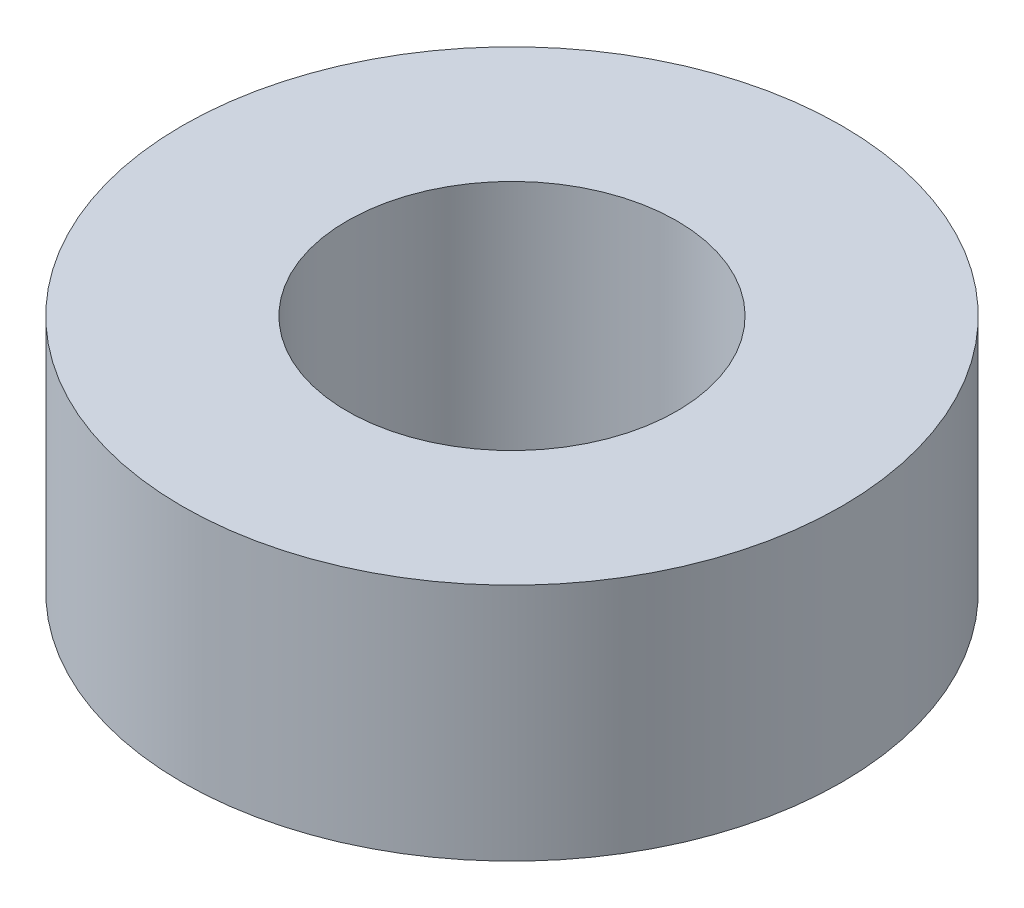
SolidWorks part; units mm, degrees
ref_plane "Front Plane" through (0, 0, 0) normal (0, 0, 1) x (1, 0, 0)
ref_plane "Top Plane" through (0, 0, 0) normal (0, 1, 0) x (1, 0, 0)
ref_plane "Right Plane" through (0, 0, 0) normal (1, 0, 0) x (0, 0, -1)
sketch "Sketch1" plane through (0, 0, 0) normal (0, 1, 0) x (1, 0, 0)
  circle A0 centre (0, 0) radius 40
  dimension "FLANGE_OD" = 80
extrude "Boss-Extrude1" add sketch "Sketch1" along normal blind 29
sketch "Sketch2" plane through (0, 0, 0) normal (0, 1, 0) x (1, 0, 0)
  circle A0 centre (0, 0) radius 20
  dimension "BORE_D" = 40
extrude "Cut-Extrude1" cut sketch "Sketch2" along normal through all
sketch "Sketch3" plane through (0, 29, 0) normal (0, 1, 0) x (1, 0, 0)
  circle A0 centre (0, 0) radius 13.8552 construction
  circle A1 centre (-13.8552, 0) radius 3.2607
  dimension "BOLT_D" = 6.5214
  dimension "BOLT_PCD" = 27.7105
extrude "Cut-Extrude2" cut sketch "Sketch3" against normal blind 17.9323 rebuild error yes
pattern_circular "CirPattern1" count 5 over 360 rebuild error yes
